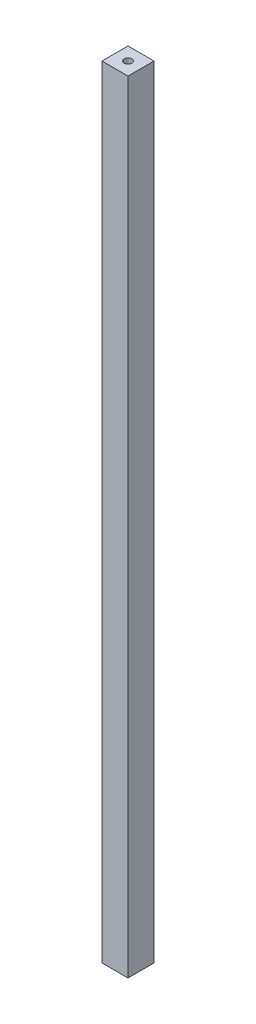
SolidWorks part; units mm, degrees
ref_plane "Front Plane" through (0, 0, 0) normal (0, 0, 1) x (1, 0, 0)
ref_plane "Top Plane" through (0, 0, 0) normal (0, 1, 0) x (1, 0, 0)
ref_plane "Right Plane" through (0, 0, 0) normal (1, 0, 0) x (0, 0, -1)
sketch "Sketch1" plane through (0, 0, 0) normal (0, 1, 0) x (1, 0, 0)
  line L1 (0, 0) -> (10, 0)
  line L2 (0, 0) -> (0, 10)
  line L3 (0, 10) -> (10, 10)
  line L4 (10, 0) -> (10, 10)
  dimension "D1" = 10
extrude "Boss-Extrude1" add sketch "Sketch1" along normal blind 300
hole_wizard "#32 (0.116) Diameter Hole1" positions "Sketch2" profile "Sketch3" hole size "#32" standard "ANSI Inch" end condition through all
sketch "Sketch2" plane through (0, 300, 0) normal (0, 1, 0) x (1, 0, 0)
  line L0 (0, 10) -> (10, 0) construction
  line L2 (10, 10) -> (0, 0) construction
  point P13 (5, 5)
sketch "Sketch3" plane through (5, 300, -5) normal (1, 0, 0) x (0, 0, 1)
  line L0 (0, 0) -> (0, 300)
  line L1 (0, 300) -> (1.4732, 300)
  line L2 (1.4732, 300) -> (1.4732, 0)
  line L5 (1.4732, 0) -> (0, 0)
  line L11 (0, -6.35) -> (0, 107.95) construction
  dimension "Thru Hole Dia." = 2.9464
  dimension "Thru Hole Depth" = 300
